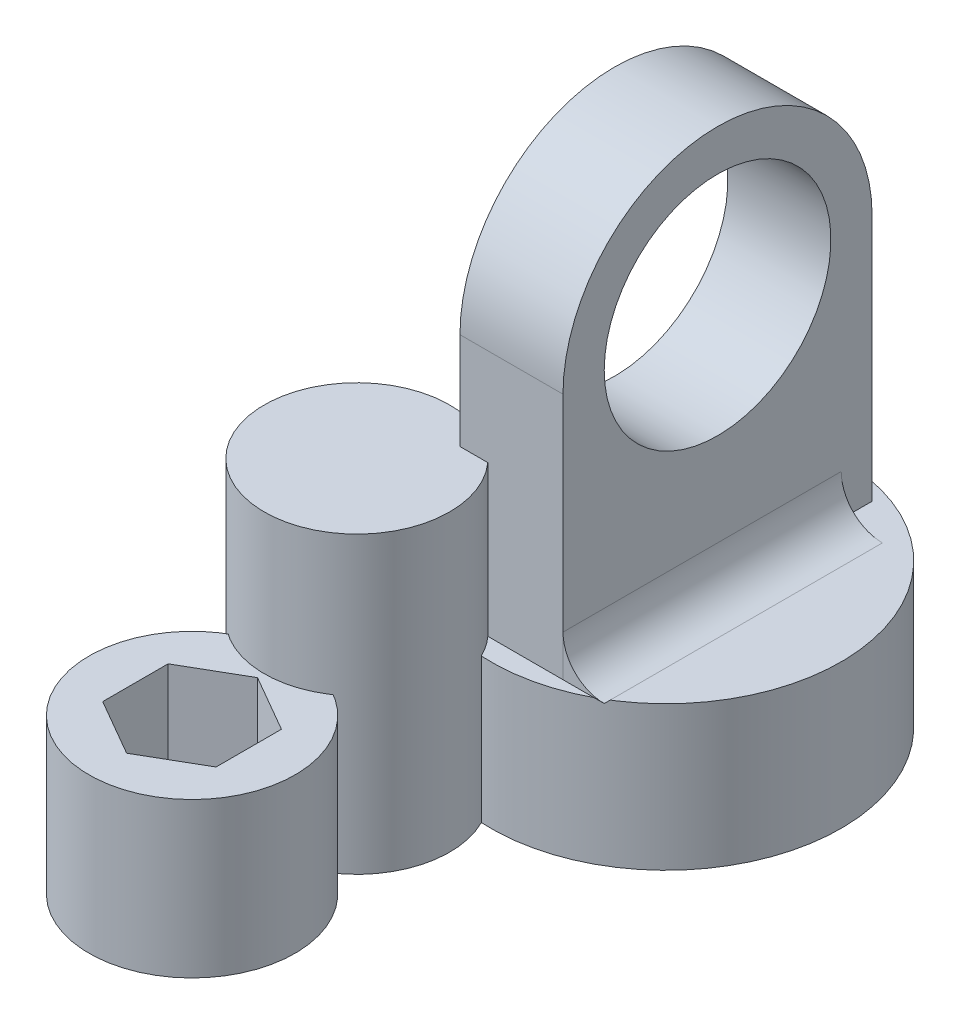
SolidWorks part; units mm, degrees
ref_plane "Front" through (0, 0, 0) normal (0, 0, 1) x (1, 0, 0)
ref_plane "Top" through (0, 0, 0) normal (0, 1, 0) x (1, 0, 0)
ref_plane "Right" through (0, 0, 0) normal (1, 0, 0) x (0, 0, -1)
sketch "Эскиз1" plane through (0, 0, 0) normal (0, 1, 0) x (1, 0, 0)
  circle A0 centre (0, 0) radius 5.5
  circle A1 centre (0, 0) radius 8.5
  dimension "D2" = 17
  dimension "D1" = 11
extrude "Бобышка-Вытянуть1" add sketch "Эскиз1" along normal blind 5
sketch "Эскиз2" plane through (0, 0, 0) normal (0, -1, 0) x (1, 0, 0)
  circle A0 centre (-4.5, 10.5) radius 1.5
  circle A1 centre (-4.5, 10.5) radius 4.5
  point P2 (-4.5, 10.5)
  dimension "D1" = 3
  dimension "D2" = 9
extrude "Бобышка-Вытянуть2" add sketch "Эскиз2" against normal up to surface (12.3 mm away)
sketch "Эскиз3" plane through (0, 12.3, 0) normal (0, 1, 0) x (1, 0, 0)
  circle A0 centre (-4.5, -10.5) radius 4.5
  dimension "D1" = 9
extrude "Бобышка-Вытянуть3" add sketch "Эскиз3" along normal blind 2
sketch "Эскиз4" plane through (0, 5, 0) normal (0, 1, 0) x (1, 0, 0)
  circle A0 centre (0, 0) radius 8.5
  circle A1 centre (0, 0) radius 8.5 construction
extrude "Бобышка-Вытянуть4" add sketch "Эскиз4" along normal blind 2
sketch "Эскиз5" plane through (0, -72.7, 0) normal (-1, 0, 0) x (0, 0, -1)
  line L0 (0, -72.7) -> (0, -61.4757) construction
  line L1 (-8.5, -79.7) -> (8.5, -79.7) construction
  line L3 (-7.5, -91.7) -> (-7.5, -79.7)
  line L4 (-7.5, -79.7) -> (7.5, -79.7)
  line L5 (7.5, -79.7) -> (7.5, -91.7)
  circle A0 centre (0, -91.7) radius 7.5
  circle A1 centre (0, -91.7) radius 5.5
  dimension "D1" = 11
  dimension "D2" = 15
  dimension "D3" = 12
extrude "Бобышка-Вытянуть5" add sketch "Эскиз5" along normal mid plane 5 contours A0 A1 | A0 L5 L4 L3 region at (0, 10.2841, 0) region at (0, 11.7121, 0)
sketch "Эскиз6" plane through (0, 0, -7.5) normal (0, 0, -1) x (-1, 0, 0)
  line L0 (2.5, 7) -> (2.5, 19) construction
  line L1 (8.5, 7) -> (-8.5, 7) construction
  line L2 (-2.5, 7) -> (-2.5, 19) construction
  line L3 (4.5, 7) -> (2.5, 7)
  line L4 (2.5, 7) -> (2.5, 9)
  line L5 (-2.5, 9) -> (-2.5, 7)
  line L6 (-2.5, 7) -> (-4.5, 7)
  circle A0 centre (4.5, 9) radius 2
  circle A1 centre (-4.5, 9) radius 2
  line M1 (-2.5, 19) -> (-2.5, 7)
  line M3 (2.5, 7) -> (2.5, 19)
  dimension "D1" = 4
extrude "Бобышка-Вытянуть6" add sketch "Эскиз6" against normal blind 13.5 from offset 1.5 separate body contours A0 L3 M3 | A1 L6 M1 region at (-2.9467, 7.4467, -7.5) region at (2.9467, 7.4467, -7.5) offset against normal yes
sketch "Эскиз7" plane through (0, 0, 0) normal (0, -1, 0) x (1, 0, 0)
  line L1 (-7.25, 16.9123) -> (-4.5, 15.3246)
  line L2 (-4.5, 15.3246) -> (-1.75, 16.9123)
  line L3 (-1.75, 16.9123) -> (-1.75, 20.0877)
  line L4 (-1.75, 20.0877) -> (-4.5, 21.6754)
  line L5 (-4.5, 21.6754) -> (-7.25, 20.0877)
  line L6 (-7.25, 20.0877) -> (-7.25, 16.9123)
  circle A0 centre (-4.5, 18.5) radius 2.75 construction
  circle A1 centre (-4.5, 18.5) radius 5
  point P9 (-4.5, 10.5)
  dimension "D2" = 10
  dimension "D1" = 5.5
  dimension "D3" = 8
extrude "Бобышка-Вытянуть7" add sketch "Эскиз7" against normal blind 7.5 separate body
